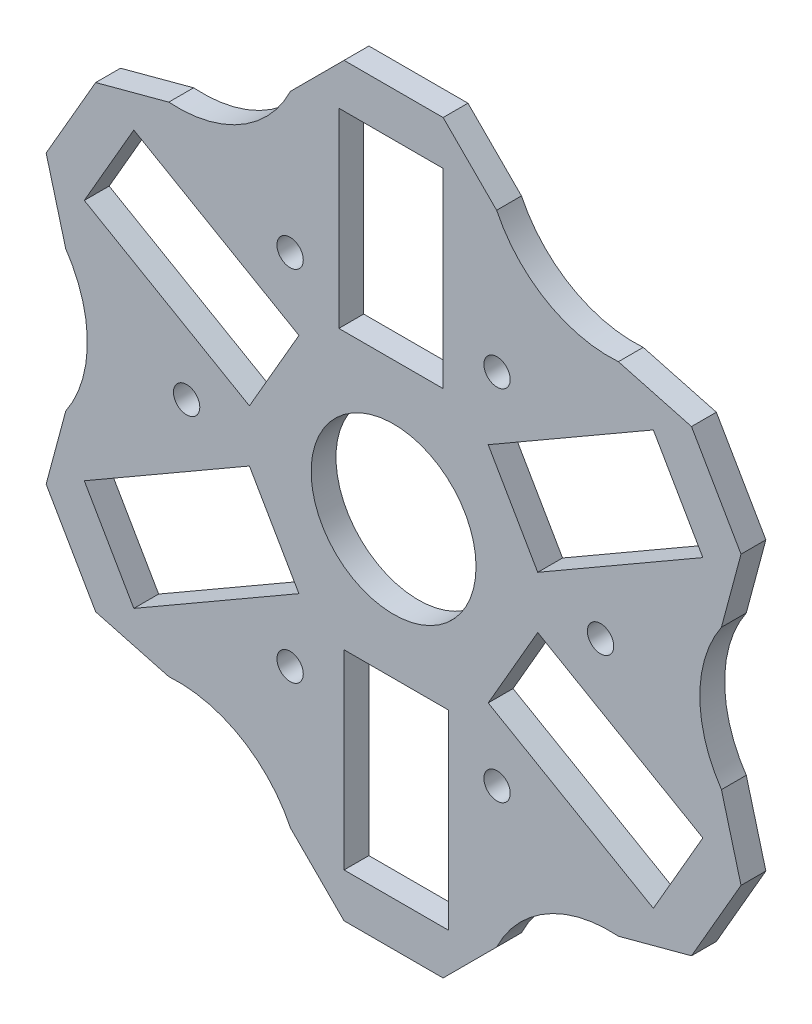
SolidWorks part; units mm, degrees
ref_plane "Front Plane" through (0, 0, 0) normal (0, 0, 1) x (1, 0, 0)
ref_plane "Top Plane" through (0, 0, 0) normal (0, 1, 0) x (1, 0, 0)
ref_plane "Right Plane" through (0, 0, 0) normal (1, 0, 0) x (0, 0, -1)
sketch "Sketch1" plane through (0, 0, 0) normal (0, 0, 1) x (1, 0, 0)
  line L0 (98.2535, -20.435) -> (104.2343, -10.076)
  line L1 (104.2343, -10.076) -> (113.0649, -7.7099)
  line L3 (127.7698, 0.78) -> (134.2343, 7.2445)
  line L4 (134.2343, 7.2445) -> (146.1958, 7.2445)
  line L5 (146.1958, 7.2445) -> (152.6602, 0.78)
  line L7 (167.3652, -7.7098) -> (176.1958, -10.076)
  line L8 (176.1958, -10.076) -> (182.1765, -20.435)
  line L9 (182.1765, -20.435) -> (179.8104, -29.2656)
  line L11 (179.8104, -46.2454) -> (182.1765, -55.076)
  line L12 (182.1765, -55.076) -> (176.1958, -65.435)
  line L13 (176.1958, -65.435) -> (167.3652, -67.8011)
  line L15 (152.6603, -76.291) -> (146.1958, -82.7555)
  line L16 (146.1958, -82.7555) -> (134.2343, -82.7555)
  line L17 (134.2343, -82.7555) -> (127.7698, -76.291)
  line L19 (113.0649, -67.8012) -> (104.2343, -65.435)
  line L20 (104.2343, -65.435) -> (98.2535, -55.076)
  line L21 (98.2535, -55.076) -> (100.6197, -46.2454)
  line L23 (100.6197, -29.2656) -> (98.2535, -20.435)
  arc A0 (113.0649, -7.7099) -> (127.7698, 0.78) centre (114.1677, 7.3599) ccw
  arc A1 (100.6197, -29.2656) -> (100.6197, -46.2454) centre (88.1203, -37.7555) cw
  arc A2 (113.0649, -67.8012) -> (127.7698, -76.291) centre (114.1677, -82.8709) cw
  arc A3 (152.6603, -76.291) -> (167.3652, -67.8011) centre (166.2624, -82.8709) cw
  arc A4 (179.8104, -29.2656) -> (179.8104, -46.2454) centre (192.3097, -37.7555) ccw
  arc A5 (152.6602, 0.78) -> (167.3652, -7.7098) centre (166.2624, 7.3599) ccw
extrude "Boss-Extrude1" add sketch "Sketch1" along normal blind 1.5 and the other way blind 1.5
sketch "Sketch2" plane through (0, 0, 1.5) normal (0, 0, 1) x (1, 0, 0)
  line L0 (133.6058, -21.1055) -> (146.1958, -21.1055)
  line L1 (146.1958, 1.9245) -> (133.6058, 1.9245)
  line L2 (133.6058, 1.9245) -> (133.6058, -21.1055)
  line L3 (146.1958, -21.1055) -> (146.1958, 1.9245)
extrude "Cut-Extrude1" cut sketch "Sketch2" against normal blind 3 contours L3 L1 L2 L0
sketch "Sketch3" plane through (0, 0, 1.5) normal (0, 0, 1) x (1, 0, 0)
  line L8 (134.2343, -54.4055) -> (146.8243, -54.4055)
  line L9 (134.2343, -54.4055) -> (134.2343, -77.4355)
  line L10 (134.2343, -77.4355) -> (146.8243, -77.4355)
  line L11 (146.8243, -54.4055) -> (146.8243, -77.4355)
extrude "Cut-Extrude2" cut sketch "Sketch3" against normal blind 3 contours L9 L8 L11 L10
sketch "Sketch4" plane through (0, 0, 1.5) normal (0, 0, 1) x (1, 0, 0)
  line L0 (171.5885, -12.736) -> (151.644, -24.251)
  line L3 (177.5693, -23.095) -> (157.6247, -34.61)
  line L4 (171.5885, -12.736) -> (177.5693, -23.095)
  line L5 (177.5693, -23.095) -> (157.6247, -34.61)
  line L6 (157.6247, -34.61) -> (151.644, -24.251)
extrude "Cut-Extrude3" cut sketch "Sketch4" against normal blind 3 contours L5 L4 L0 L6
sketch "Sketch5" plane through (0, 0, 1.5) normal (0, 0, 1) x (1, 0, 0)
  line L0 (102.8607, -52.416) -> (122.8053, -40.901)
  line L1 (108.8415, -62.775) -> (128.7861, -51.26)
  line L2 (122.8053, -40.901) -> (128.7861, -51.26)
  line L3 (102.8607, -52.416) -> (108.8415, -62.775)
extrude "Cut-Extrude4" cut sketch "Sketch5" against normal blind 3 contours L1 L2 L0 L3
sketch "Sketch6" plane through (0, 0, 1.5) normal (0, 0, 1) x (1, 0, 0)
  line L0 (108.8415, -12.736) -> (128.7861, -24.251)
  line L1 (102.8608, -23.095) -> (122.8053, -34.61)
  line L2 (128.7861, -24.251) -> (122.8053, -34.61)
  line L3 (108.8415, -12.736) -> (102.8608, -23.095)
extrude "Cut-Extrude5" cut sketch "Sketch6" against normal blind 3 contours L1 L2 L0 L3
sketch "Sketch7" plane through (0, 0, 1.5) normal (0, 0, 1) x (1, 0, 0)
  line L1 (151.644, -51.26) -> (171.5885, -62.775)
  line L2 (177.5693, -52.416) -> (171.5885, -62.775)
  line L3 (177.5693, -52.416) -> (157.6247, -40.901)
  line L4 (157.6247, -40.901) -> (151.644, -51.26)
extrude "Cut-Extrude6" cut sketch "Sketch7" against normal blind 3
sketch "Sketch8" plane through (0, 0, 1.5) normal (0, 0, 1) x (1, 0, 0)
  circle A0 centre (140.215, -37.7555) radius 9.96
extrude "Cut-Extrude7" cut sketch "Sketch8" against normal blind 3
sketch "Sketch9" plane through (0, 0, 1.5) normal (0, 0, 1) x (1, 0, 0)
  circle A2 centre (127.7177, -59.4016) radius 1.59
extrude "Cut-Extrude8" cut sketch "Sketch9" against normal up to vertex (3 mm away) up to point (127.7698, -76.291, -1.5)
sketch "Sketch10" plane through (0, 0, 1.5) normal (0, 0, 1) x (1, 0, 0)
  circle A0 centre (152.7124, -16.1094) radius 1.59
  circle A4 centre (165.2097, -37.7555) radius 1.59
  circle A6 centre (115.2203, -37.7555) radius 1.59
  circle A7 centre (127.7177, -16.1094) radius 1.59
  circle A8 centre (152.7124, -59.4016) radius 1.59
extrude "Cut-Extrude9" cut sketch "Sketch10" against normal up to vertex (3 mm away) up to point (152.6602, 0.78, -1.5)
